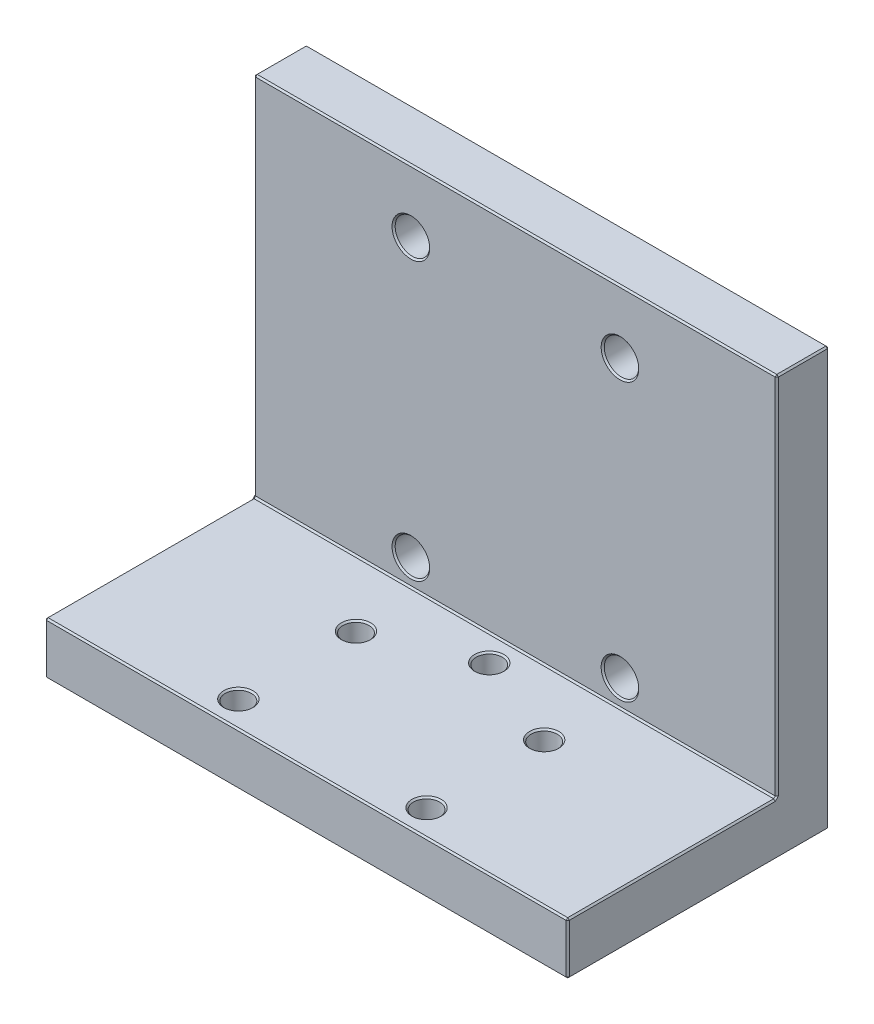
SolidWorks part; units mm, degrees
material "1060 Alloy"
ref_plane "Front Plane" through (0, 0, 0) normal (0, 0, 1) x (1, 0, 0)
ref_plane "Top Plane" through (0, 0, 0) normal (0, 1, 0) x (1, 0, 0)
ref_plane "Right Plane" through (0, 0, 0) normal (1, 0, 0) x (0, 0, -1)
sketch "Sketch1" plane through (0, 0, 0) normal (1, 0, 0) x (0, 0, -1)
  line L2 (0, 0) -> (0, 80)
  line L3 (0, 80) -> (-10, 80)
  line L4 (-10, 10) -> (-10, 80)
  line L5 (0, 0) -> (-50, 0)
  line L7 (-10, 10) -> (-50, 10)
  line L8 (-50, 0) -> (-50, 10)
  dimension "D1" = 10
  dimension "D2" = 80
  dimension "D3" = 50
extrude "Boss-Extrude1" add sketch "Sketch1" along normal mid plane 100
sketch "Sketch2" plane through (0, 0, 10) normal (0, 0, 1) x (1, 0, 0)
  line L0 (50, 0) -> (-50, 0) construction
  line L1 (20, 15) -> (-20, 15) construction
  line L2 (20, 15) -> (20, 68) construction
  line L3 (20, 68) -> (-20, 68) construction
  line L4 (-20, 15) -> (-20, 68) construction
  line L5 (20, 15) -> (-20, 68) construction
  line L6 (20, 68) -> (-20, 15) construction
  line L7 (50, 80) -> (50, 10) construction
  line L8 (0, 41.5) -> (0, 0) construction
  line L9 (-50, 80) -> (50, 80) construction
  line L10 (-50, 80) -> (-50, 0) construction
  line L11 (-50, 0) -> (50, 0) construction
  line L12 (50, 80) -> (50, 0) construction
  line L13 (-50, 80) -> (-50, 10) construction
  circle A0 centre (-20, 68) radius 3.3
  circle A1 centre (20, 68) radius 3.3
  circle A2 centre (20, 15) radius 3.3
  circle A3 centre (-20, 15) radius 3.3
  point P0 (0, 41.5)
  dimension "D1" = 6.6
  dimension "D2" = 40
  dimension "D3" = 53
  dimension "D5" = 80
  dimension "D4" = 15
extrude "Cut-Extrude1" cut sketch "Sketch2" against normal blind 100
sketch "Sketch3" plane through (0, 10, 0) normal (0, 1, 0) x (1, 0, 0)
  line L0 (0, 0) -> (0, -33.75) construction
  line L1 (18, -22.5) -> (-18, -22.5) construction
  line L2 (18, -22.5) -> (18, -45) construction
  line L3 (18, -45) -> (-18, -45) construction
  line L4 (-18, -22.5) -> (-18, -45) construction
  line L5 (18, -22.5) -> (-18, -45) construction
  line L6 (18, -45) -> (-18, -22.5) construction
  line L9 (50, 0) -> (-50, 0) construction
  circle A0 centre (-18, -22.5) radius 2.5
  circle A1 centre (-18, -45) radius 2.5
  circle A2 centre (18, -45) radius 2.5
  circle A3 centre (18, -22.5) radius 2.5
  circle A4 centre (0, -15) radius 2.5
  point P0 (0, -33.75)
  dimension "D1" = 5
  dimension "D2" = 22.5
  dimension "D3" = 36
  dimension "D4" = 7.5
  dimension "D5" = 15
extrude "Cut-Extrude2" cut sketch "Sketch3" against normal blind 100
chamfer "Chamfer1" distance 0.3 angle 45 36 edges at (-18, 10, 25) (-18, 10, 47.5) (18, 10, 47.5) (18, 10, 25) (0, 10, 17.5) (-16.7, 68, 10) (23.3, 68, 10) (23.3, 15, 10) (-16.7, 15, 10) (50, 10, 30) (0, 10, 50) (-50, 10, 30) (0, 80, 10) (50, 45, 10) (0, 10, 10) (-50, 45, 10) (0, 0, 0) (0, 80, 0) (50, 5, 50) (50, 80, 5) (50, 40, 0) (50, 0, 25) (0, 0, 50) (-50, 5, 50) (-50, 80, 5) (-50, 40, 0) (-50, 0, 25) (-16.7, 68, 0) (23.3, 68, 0) (23.3, 15, 0) (-16.7, 15, 0) (-18, 0, 25) (-18, 0, 47.5) (18, 0, 47.5) (18, 0, 25) (0, 0, 17.5)
equation "\"M5_tap\"=4.2mm"
equation "\"M5_clearence\"=5.5mm"
equation "\"M6_tap\"=5mm"
equation "\"M6_clearence\"=6.6mm"
equation "\"D1@Sketch2\"=\"M6_clearence\""
equation "\"D1@Sketch3\"=\"M6_tap\""
equation "\"work_area_width\"=1100mm"
equation "\"work_area_depth\"=900mm"
equation "\"steel_base_width\"=80mm"
equation "\"steel_base_height\"=50mm"
equation "\"steel_base_wall_thickness\"=3mm"
equation "\"steel_base_radius\"=6mm"
equation "\"steel_sides_width\"=80mm"
equation "\"steel_sides_height\"=50mm"
equation "\"steel_sides_wall_thickness\"=5mm"
equation "\"steel_sides_radius\"=6mm"
equation "\"steel_gantry_width\"=80mm"
equation "\"steel_gantry_height\"=50mm"
equation "\"steel_gantry_wall_thickness\"=6mm"
equation "\"steel_gantry_radius\"=6mm"
equation "\"steel_rollers_width\"=80mm"
equation "\"steel_rollers_height\"=50mm"
equation "\"steel_rollers_wall_thickness\"=6mm"
equation "\"steel_rollers_radius\"=6mm"
equation "\"steel_zbox_width\"=80mm"
equation "\"steel_zbox_height\"=50mm"
equation "\"steel_zbox_wall_thickness\"=3mm"
equation "\"steel_zbox_radius\"=6mm"
equation "\"alu_zangle_width\"=80mm"
equation "\"alu_zangle_height\"=50mm"
equation "\"alu_zangle_wall_thickness\"=10mm"
equation "\"D1@Sketch1\"=\"alu_zangle_wall_thickness\""
equation "\"D2@Sketch1\"=\"alu_zangle_width\""
equation "\"D3@Sketch1\"=\"alu_zangle_height\""
equation "\"D5@Sketch2\"=\"steel_zbox_width\""
equation "\"D5@Sketch3\"=\"alu_zangle_wall_thickness\"+5"
equation "\"D4@Sketch2\"=\"alu_zangle_wall_thickness\" + 5"
